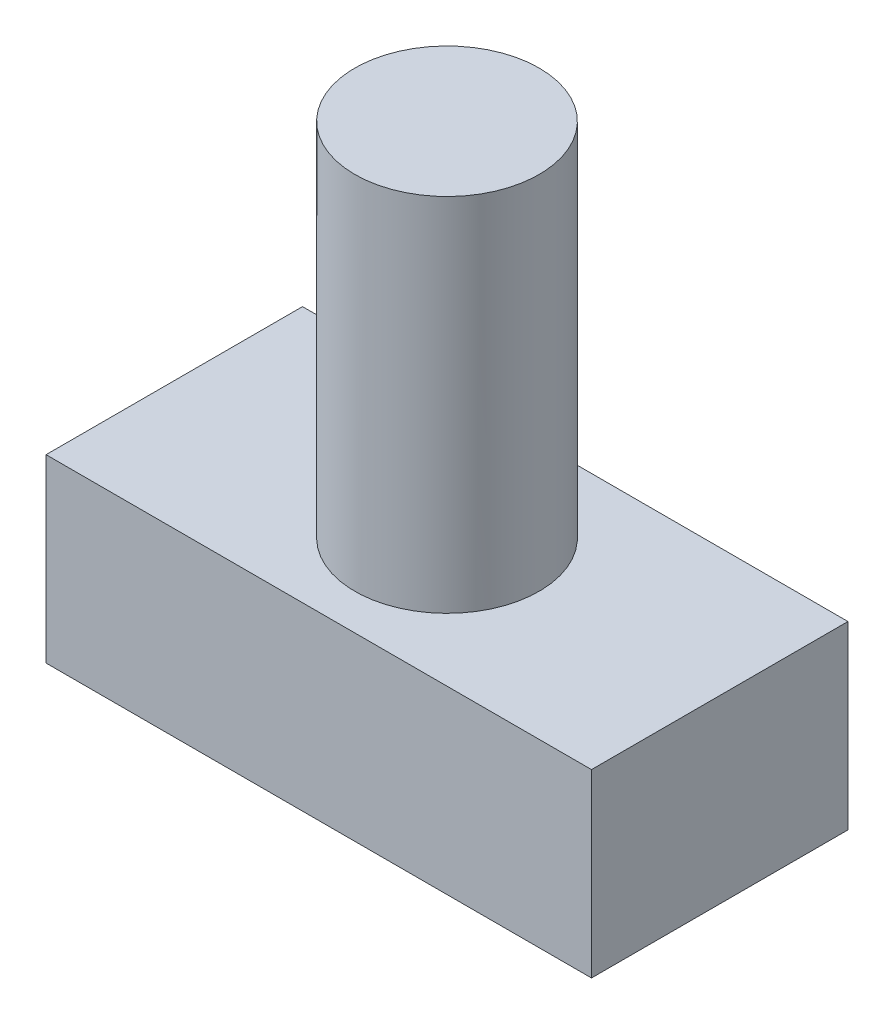
SolidWorks part; units mm, degrees
ref_plane "前视基准面" through (0, 0, 0) normal (0, 0, 1) x (1, 0, 0)
ref_plane "上视基准面" through (0, 0, 0) normal (0, 1, 0) x (1, 0, 0)
ref_plane "右视基准面" through (0, 0, 0) normal (1, 0, 0) x (0, 0, -1)
other "Configuration Table"
sketch "草图1" plane through (0, 0, 0) normal (0, 1, 0) x (1, 0, 0)
  line L0 (-40.3876, -32.9374) -> (23.6575, -13.3318)
  circle A0 centre (69.4039, -38.1656) radius 24.2828
  point P0 (-56.5949, 9.1493)
  point P1 (-19.7363, 28.4935)
  point P2 (53.1966, 16.4687)
  point P7 (69.4039, -38.1656)
curve "曲线1"
sketch "草图2" plane through (0, 0, 0) normal (0, 1, 0) x (1, 0, 0)
  line L1 (-151.0902, -71.0418) -> (151.0902, -71.0418)
  line L2 (-151.0902, -71.0418) -> (-151.0902, 71.0418)
  line L3 (-151.0902, 71.0418) -> (151.0902, 71.0418)
  line L4 (151.0902, -71.0418) -> (151.0902, 71.0418)
  line L5 (-151.0902, -71.0418) -> (151.0902, 71.0418) construction
  line L6 (-151.0902, 71.0418) -> (151.0902, -71.0418) construction
  circle A0 centre (0, 0) radius 51.0782
extrude "凸台-拉伸1" add sketch "草图2" along normal blind 100 contours L1 L4 L3 L2
extrude "凸台-拉伸2" add sketch "草图2<3>" along normal blind 300 contours A0
sketch "草图2<3>" plane through (0, 0, 0) normal (0, 1, 0) x (1, 0, 0) same geometry as "草图2"
curve "曲线2"
sketch3d "3D草图1"
  spline S0 degree 3 poles (0, 0, 0) (188.6171, -177.302, -3.9502) (124.3613, 171.8079, 192.7938) (205.2805, 45.2208, -225.1631) (-184.1993, 247.1489, 78.3162) (-135.9338, -135.842, 91.7219) (-156.6269, 245.9089, -144.0949) (-151.0902, 0, -71.0418) knots 0 0 0 0 0.239059 0.366294 0.665314 0.754863 1 1 1 1
